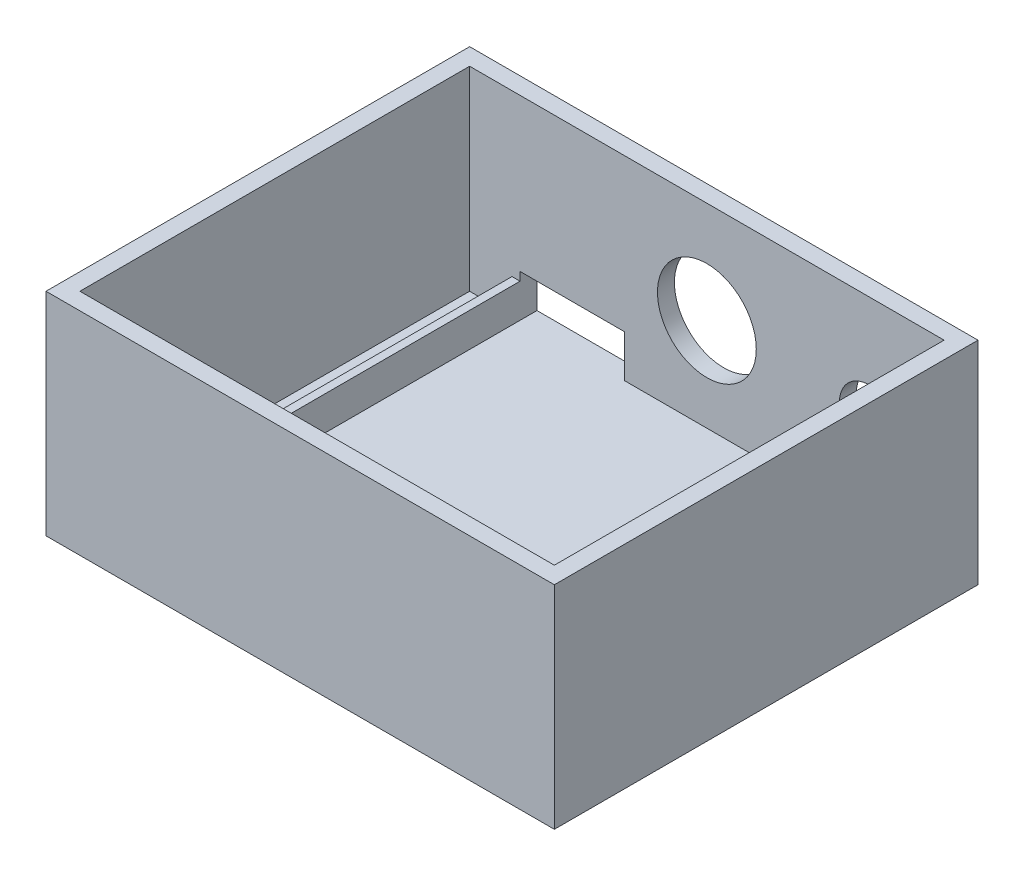
SolidWorks part; units mm, degrees
ref_plane "Front Plane" through (0, 0, 0) normal (0, 0, 1) x (1, 0, 0)
ref_plane "Top Plane" through (0, 0, 0) normal (0, 1, 0) x (1, 0, 0)
ref_plane "Right Plane" through (0, 0, 0) normal (1, 0, 0) x (0, 0, -1)
sketch "Sketch1" plane through (0, 0, 0) normal (0, 1, 0) x (1, 0, 0)
  line L1 (-70.5712, -39.9173) -> (49.4288, -39.9173)
  line L2 (-70.5712, -39.9173) -> (-70.5712, 60.0827)
  line L3 (-70.5712, 60.0827) -> (49.4288, 60.0827)
  line L4 (49.4288, -39.9173) -> (49.4288, 60.0827)
  dimension "D1" = 120
  dimension "D2" = 100
extrude "Boss-Extrude1" add sketch "Sketch1" along normal blind 50
sketch "Sketch2" plane through (0, 50, 0) normal (0, 1, 0) x (1, 0, 0)
  line L0 (49.4288, 60.0827) -> (-70.5712, 60.0827) construction
  line L1 (-66.5712, 56.0827) -> (45.4288, 56.0827)
  line L2 (-66.5712, 56.0827) -> (-66.5712, -35.9173)
  line L3 (-66.5712, -35.9173) -> (45.4288, -35.9173)
  line L4 (45.4288, 56.0827) -> (45.4288, -35.9173)
  line L5 (-70.5712, -39.9173) -> (49.4288, -39.9173) construction
  line L6 (-70.5712, 60.0827) -> (-70.5712, -39.9173) construction
  line L7 (49.4288, -39.9173) -> (49.4288, 60.0827) construction
  dimension "D1" = 4
  dimension "D2" = 4
  dimension "D3" = 4
  dimension "D4" = 4
extrude "Cut-Extrude1" cut sketch "Sketch2" against normal blind 46
sketch "Sketch3" plane through (0, 4, 0) normal (0, 1, 0) x (1, 0, 0)
  line L0 (-66.5712, 56.0827) -> (-66.5712, -35.9173) construction
  line L1 (49.4288, 60.0827) -> (-70.5712, 60.0827) construction
  line L2 (-56.5712, 60.0827) -> (-31.9712, 60.0827)
  line L3 (-56.5712, 60.0827) -> (-56.5712, -9.9173)
  line L4 (-56.5712, -9.9173) -> (-31.9712, -9.9173)
  line L5 (-31.9712, 60.0827) -> (-31.9712, -9.9173)
  dimension "D1" = 24.6
  dimension "D2" = 70
  dimension "D3" = 10
extrude "Boss-Extrude3" add sketch "Sketch3" along normal blind 8
sketch "Sketch6" plane through (0, 0, 9.9173) normal (0, 0, 1) x (1, 0, 0)
  line L0 (-56.5712, 12) -> (-31.9712, 12) construction
  line L1 (-54.6743, 12) -> (-30.0643, 12)
  line L2 (-54.6743, 12) -> (-54.6743, 4)
  line L3 (-54.6743, 4) -> (-30.0643, 4)
  line L4 (-30.0643, 12) -> (-30.0643, 4)
  line L5 (-66.5712, 4) -> (45.4288, 4) construction
  dimension "D1" = 24.61
extrude "Cut-Extrude4" cut sketch "Sketch6" against normal blind 66
sketch "Sketch7" plane through (0, 0, -56.0827) normal (0, 0, 1) x (1, 0, 0)
  line L3 (-54.6743, 4) -> (-30.0743, 4)
  line L4 (-54.6743, 4) -> (-54.6743, 14)
  line L5 (-54.6743, 14) -> (-30.0743, 14)
  line L6 (-30.0743, 4) -> (-30.0743, 14)
  dimension "D1" = 24.6
  dimension "D2" = 10
extrude "Cut-Extrude6" cut sketch "Sketch7" against normal blind 66
sketch "Sketch8" plane through (0, 0, -56.0827) normal (0, 0, 1) x (1, 0, 0)
  line L6 (45.4288, 50) -> (-66.5712, 50) construction
  line L7 (-66.5712, 4) -> (-66.5712, 50) construction
  circle A0 centre (-10.5712, 26) radius 11.6622
  dimension "D5" = 24
  dimension "D6" = 56
sketch "Sketch10" plane through (0, 0, -60.0827) normal (0, 0, -1) x (-1, 0, 0)
  line L0 (-49.4288, 50) -> (-49.4288, 0) construction
  line L2 (-50.6638, 25) -> (89.3617, 25) construction
  circle A0 centre (-27.7288, 25) radius 7
  dimension "D1" = 21.7
extrude "Cut-Extrude9" cut sketch "Sketch10" against normal blind 12.5
extrude "Cut-Extrude10" cut sketch "Sketch8" against normal blind 10
